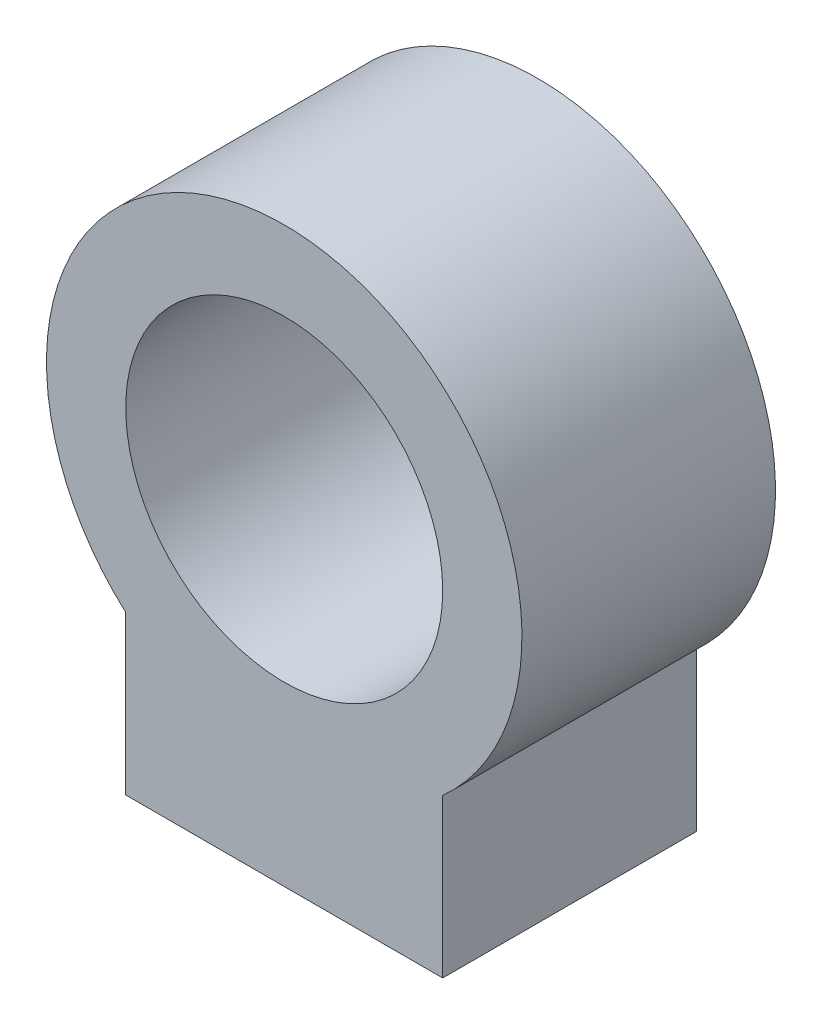
SolidWorks part; units mm, degrees
ref_plane "Front Plane" through (0, 0, 0) normal (0, 0, 1) x (1, 0, 0)
ref_plane "Top Plane" through (0, 0, 0) normal (0, 1, 0) x (1, 0, 0)
ref_plane "Right Plane" through (0, 0, 0) normal (1, 0, 0) x (0, 0, -1)
sketch "Sketch1" plane through (0, 0, 0) normal (0, 1, 0) x (1, 0, 0)
  line L1 (-25, 20) -> (25, 20)
  line L2 (-25, 20) -> (-25, -20)
  line L3 (-25, -20) -> (25, -20)
  line L4 (25, 20) -> (25, -20)
  line L5 (-25, 20) -> (25, -20) construction
  line L6 (-25, -20) -> (25, 20) construction
  point P0 (0, 0)
  dimension "D1" = 50
  dimension "D2" = 40
extrude "Boss-Extrude1" add sketch "Sketch1" along normal blind 25
sketch "Sketch2" plane through (0, 0, 0) normal (0, 0, 1) x (1, 0, 0)
  line L0 (0, 0) -> (0, 52.9) construction
  line L1 (-25, 25) -> (25, 25) construction
  circle A0 centre (0, 52.9) radius 37.5
  dimension "D2" = 75
  dimension "D1" = 27.9
extrude "Boss-Extrude2" add sketch "Sketch2" along normal blind 20 and the other way blind 20
sketch "Sketch3" plane through (0, 0, 0) normal (0, 0, 1) x (1, 0, 0)
  circle A0 centre (0, 52.9) radius 25
  dimension "D1" = 50
extrude "Cut-Extrude1" cut sketch "Sketch3" against normal blind 20 and the other way blind 20
ref_axis "Axis1" through (0, -4.52, 0) along (0, 1, 0)
ref_axis "Axis2" through (0, 52.9, 20) along (0, 0, -1)
